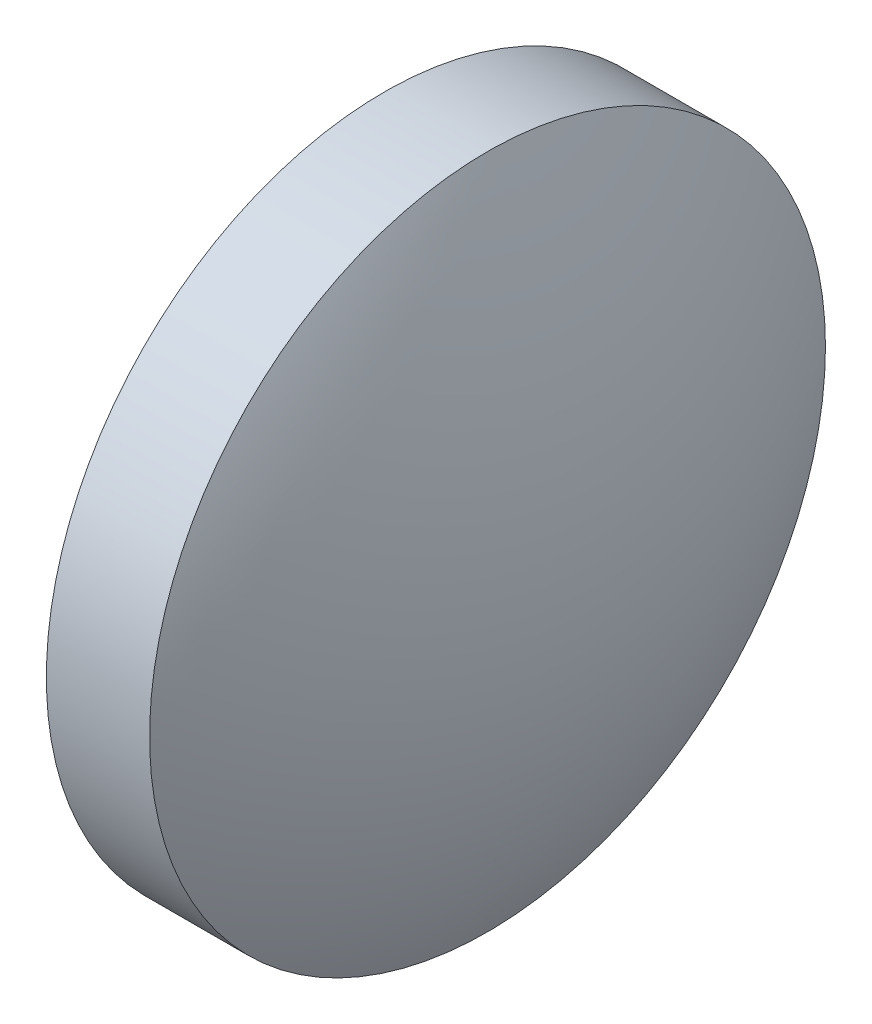
SolidWorks part; units mm, degrees
material "Ceramic Porcelain"
ref_plane "Front Plane" through (0, 0, 0) normal (0, 0, 1) x (1, 0, 0)
ref_plane "Top Plane" through (0, 0, 0) normal (0, 1, 0) x (1, 0, 0)
ref_plane "Right Plane" through (0, 0, 0) normal (1, 0, 0) x (0, 0, -1)
sketch "Sketch1" plane through (0, 0, 0) normal (1, 0, 0) x (0, 0, -1)
  circle A0 centre (0, 0) radius 8.185
  dimension "D1" = 16.37
extrude "Boss-Extrude1" add sketch "Sketch1" along normal blind 2.5
dome "Dome1" faces to dome 1 distance 2 reverse direction no elliptical dome no face at (2.5, 0, -8.185) parameters "D1"=2
